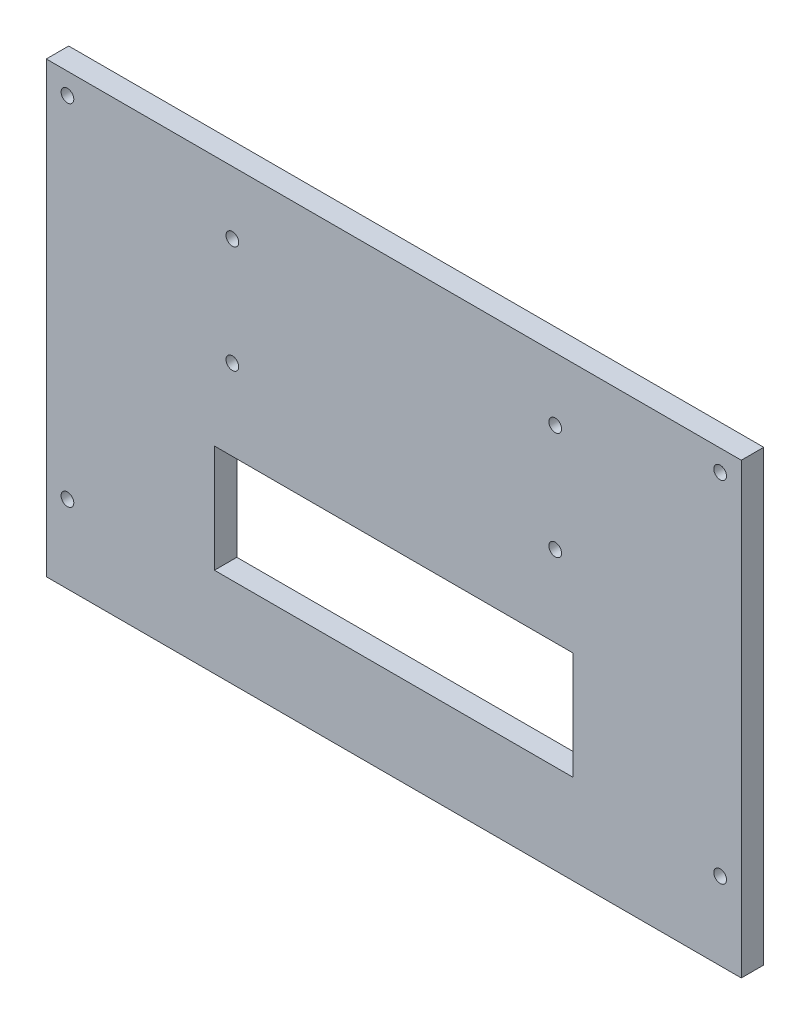
SolidWorks part; units mm, degrees
material "Acrylic (Medium-high impact)"
ref_plane "Front Plane" through (0, 0, 0) normal (0, 0, 1) x (1, 0, 0)
ref_plane "Top Plane" through (0, 0, 0) normal (0, 1, 0) x (1, 0, 0)
ref_plane "Right Plane" through (0, 0, 0) normal (1, 0, 0) x (0, 0, -1)
sketch "Sketch1" plane through (0, 0, 0) normal (0, 0, 1) x (1, 0, 0)
  line L1 (196.85, 127) -> (0, 127)
  line L2 (196.85, 127) -> (196.85, 0)
  line L3 (196.85, 0) -> (0, 0)
  line L4 (0, 127) -> (0, 0)
  line L5 (196.85, 127) -> (0, 0) construction
  line L6 (196.85, 0) -> (0, 127) construction
  point P0 (98.425, 63.5)
  dimension "D1" = 127
  dimension "D2" = 196.85
extrude "Boss-Extrude1" add sketch "Sketch1" along normal blind 6.35
hole_wizard "M3 Clearance Hole1" positions "Sketch2" profile "Sketch3" hole size "M3" standard "ANSI Metric" end condition through all
sketch "Sketch2" plane through (0, 0, 6.35) normal (0, 0, 1) x (1, 0, 0)
  line L0 (0, 127) -> (0, 0) construction
  line L1 (196.85, 127) -> (0, 127) construction
  line L2 (196.85, 0) -> (196.85, 127) construction
  line L3 (0, 0) -> (196.85, 0) construction
  point P0 (5.9944, 121.0056)
  point P2 (5.9944, 21.9964)
  point P4 (190.8556, 21.9964)
  point P6 (190.8556, 121.0056)
  dimension "D1" = 5.9944
  dimension "D2" = 5.9944
  dimension "D3" = 5.9944
  dimension "D4" = 21.9964
sketch "Sketch3" plane through (5.9944, 121.0056, 6.35) normal (1, 0, 0) x (0, -1, 0)
  line L0 (0, 0) -> (0, 6.35)
  line L1 (0, 6.35) -> (1.8, 6.35)
  line L2 (1.8, 6.35) -> (1.8, 0)
  line L5 (1.8, 0) -> (0, 0)
  line L11 (0, -6.35) -> (0, 107.95) construction
  dimension "Thru Hole Dia." = 3.6
  dimension "Thru Hole Depth" = 6.35
sketch "Sketch4" plane through (0, 0, 6.35) normal (0, 0, 1) x (1, 0, 0)
  line L0 (0, 127) -> (0, 0) construction
  line L1 (46.99, 107.95) -> (50.4952, 107.95)
  line L2 (46.99, 107.95) -> (46.99, 44.45)
  line L3 (46.99, 44.45) -> (50.4952, 44.45)
  line L4 (50.4952, 107.95) -> (50.4952, 44.45)
  line L5 (146.3548, 107.95) -> (149.86, 107.95)
  line L6 (146.3548, 107.95) -> (146.3548, 44.45)
  line L7 (146.3548, 44.45) -> (149.86, 44.45)
  line L8 (149.86, 107.95) -> (149.86, 44.45)
  line L9 (196.85, 0) -> (196.85, 127) construction
  line L10 (196.85, 127) -> (0, 127) construction
  dimension "D1" = 3.5052
  dimension "D2" = 63.5
  dimension "D3" = 46.99
  dimension "D4" = 46.99
  dimension "D5" = 19.05
extrude "Cut-Extrude1" [suppressed] cut sketch "Sketch4" against normal through all
sketch "Sketch5" plane through (0, 0, 6.35) normal (0, 0, 1) x (1, 0, 0)
  line L0 (0, 36.1092) -> (76.2, 25.4)
  line L1 (0, 127) -> (0, 0) construction
  line L2 (76.2, 25.4) -> (120.65, 25.4)
  line L3 (120.65, 25.4) -> (196.85, 36.1092)
  line L4 (196.85, 0) -> (196.85, 127) construction
  line L5 (196.85, 36.1092) -> (196.85, 0)
  line L6 (196.85, 0) -> (0, 0)
  line L7 (0, 0) -> (0, 36.1092)
  dimension "D1" = 8
  dimension "D2" = 8
  dimension "D3" = 76.2
  dimension "D4" = 76.2
  dimension "D5" = 25.4
extrude "Cut-Extrude2" [suppressed] cut sketch "Sketch5" against normal through all
sketch "Sketch7" plane through (0, 0, 6.35) normal (0, 0, 1) x (1, 0, 0)
  line L0 (0, 0) -> (196.85, 0) construction
  line L1 (47.625, 55.88) -> (149.225, 55.88)
  line L2 (47.625, 55.88) -> (47.625, 25.4)
  line L3 (47.625, 25.4) -> (149.225, 25.4)
  line L4 (149.225, 55.88) -> (149.225, 25.4)
  line L5 (47.625, 55.88) -> (149.225, 25.4) construction
  line L6 (47.625, 25.4) -> (149.225, 55.88) construction
  point P0 (98.425, 40.64)
  point P5 (98.425, 0)
  dimension "D1" = 30.48
  dimension "D2" = 101.6
  dimension "D3" = 25.4
extrude "tubingslot" cut sketch "Sketch7" against normal through all
hole_wizard "M3 Clearance Hole2" positions "Sketch8" profile "Sketch9" hole size "M3" standard "ANSI Metric" end condition through all
sketch "Sketch8" plane through (0, 0, 6.35) normal (0, 0, 1) x (1, 0, 0)
  line L0 (52.705, 109.22) -> (144.145, 109.22) construction
  line L2 (98.425, 109.22) -> (98.425, 127) construction
  line L3 (196.85, 127) -> (0, 127) construction
  point P0 (52.705, 109.22)
  point P2 (144.145, 109.22)
  point P4 (52.705, 78.74)
  point P6 (144.145, 78.74)
  dimension "D1" = 91.44
  dimension "D2" = 30.48
  dimension "D3" = 17.78
sketch "Sketch9" plane through (52.705, 109.22, 6.35) normal (1, 0, 0) x (0, -1, 0)
  line L0 (0, 0) -> (0, 6.35)
  line L1 (0, 6.35) -> (1.8, 6.35)
  line L2 (1.8, 6.35) -> (1.8, 0)
  line L5 (1.8, 0) -> (0, 0)
  line L11 (0, -6.35) -> (0, 107.95) construction
  dimension "Thru Hole Dia." = 3.6
  dimension "Thru Hole Depth" = 6.35
